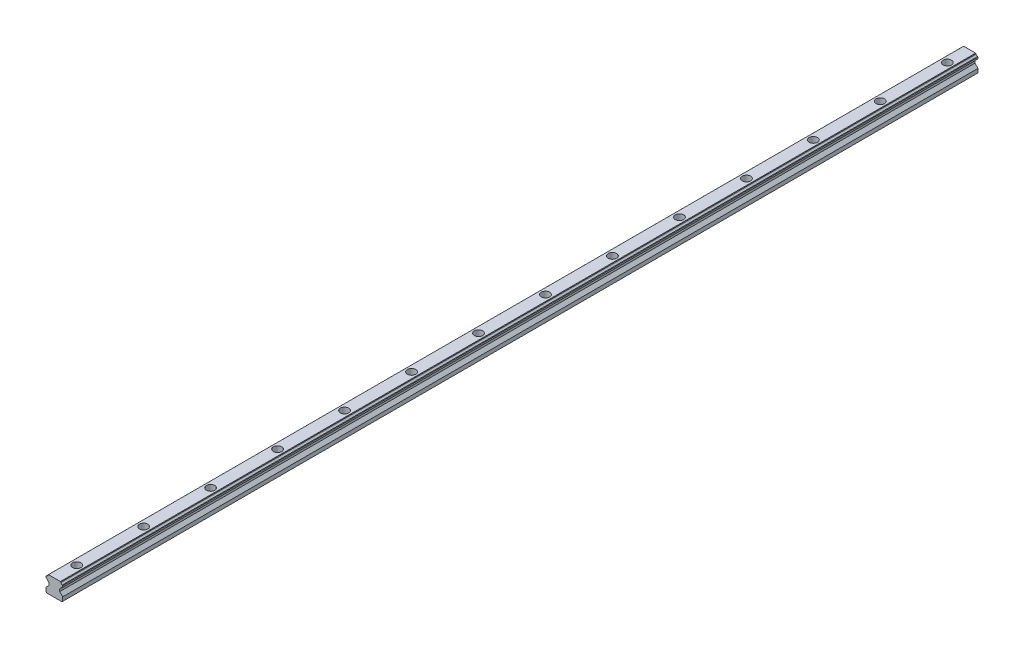
SolidWorks part; units mm, degrees
ref_plane "Front Plane" through (0, 0, 0) normal (0, 0, 1) x (1, 0, 0)
ref_plane "Top Plane" through (0, 0, 0) normal (0, 1, 0) x (1, 0, 0)
ref_plane "Right Plane" through (0, 0, 0) normal (1, 0, 0) x (0, 0, -1)
sketch "Sketch1" plane through (-20, 0, 0) normal (0, 0, 1) x (1, 0, 0)
  line L0 (12.5, 0.7) -> (13.2, 0)
  line L1 (13.2, 0) -> (26.8, 0)
  line L2 (27.5, 4.2) -> (27.5, 0.7)
  line L3 (24.8, 6.9) -> (27.5, 4.2)
  line L4 (24.8, 8.84) -> (24.8, 6.9)
  line L5 (25.7559, 9.7942) -> (24.8, 8.84)
  line L6 (27.5, 11.54) -> (27.0943, 11.1343)
  line L7 (27.5, 12.85) -> (27.5, 11.54)
  line L8 (27.0943, 13.2684) -> (27.5, 12.85)
  line L9 (25.35, 15) -> (25.7559, 14.5941)
  line L10 (27.5, 0.7) -> (26.8, 0)
  line L11 (25.35, 15) -> (14.65, 15)
  line L12 (14.65, 15) -> (14.2441, 14.5941)
  line L13 (12.9057, 13.2684) -> (12.5, 12.85)
  line L14 (12.5, 12.85) -> (12.5, 11.54)
  line L15 (12.5, 11.54) -> (12.9057, 11.1343)
  line L16 (14.2441, 9.7942) -> (15.2, 8.84)
  line L17 (15.2, 8.84) -> (15.2, 6.9)
  line L18 (15.2, 6.9) -> (12.5, 4.2)
  line L19 (12.5, 4.2) -> (12.5, 0.7)
  line L20 (20, 15) -> (20, 0) construction
  arc A0 (27.0943, 11.1343) -> (25.7559, 9.7942) centre (27.3023, 9.5882) ccw
  arc A1 (25.7559, 14.5941) -> (27.0943, 13.2684) centre (27.3003, 14.8148) ccw
  arc A2 (14.2441, 14.5941) -> (12.9057, 13.2684) centre (12.6997, 14.8148) cw
  arc A3 (12.9057, 11.1343) -> (14.2441, 9.7942) centre (12.6977, 9.5882) cw
  dimension "D14" = 1.56
  dimension "D1" = 15
  dimension "D2" = 0.7
  dimension "D3" = 0.7
  dimension "D4" = 4.2
  dimension "D5" = 6.9
  dimension "D6" = 8.84
  dimension "D7" = 4.8
  dimension "D8" = 5.7559
  dimension "D9" = 0.4059
  dimension "D10" = 0.4059
  dimension "D11" = 1.7316
  dimension "D12" = 2.15
  dimension "D13" = 3.46
  dimension "D15" = 7.0943
  dimension "D16" = 3.8657
  dimension "D17" = 5.2058
  dimension "D18" = 15
extrude "Extrude1" add sketch "Sketch1" against normal blind 820
sketch "Sketch2" plane through (0, 0, 0) normal (1, 0, 0) x (0, 0, -1)
  line L0 (20, 15) -> (23.75, 15)
  line L1 (23.75, 15) -> (23.75, 9.7)
  line L2 (23.75, 9.7) -> (22.25, 9.7)
  line L3 (22.25, 9.7) -> (22.25, 0)
  line L4 (22.25, 0) -> (20, 0)
  line L5 (20, 0) -> (20, 15) construction
  line L6 (20, 0) -> (20, 15) construction
  line L7 (20, 15) -> (20, 0)
  line L8 (820, 0) -> (0, 0) construction
  line L9 (820, 15) -> (0, 15) construction
  dimension "D1" = 5.3
  dimension "D2" = 7.5
  dimension "D3" = 4.5
  dimension "D4" = 20
revolve "Cut-Revolve1" cut sketch "Sketch2" angle 360 about L6 reverse direction yes
ref_axis "Axis1" through (0, 0, -168) along (0, 0, 1)
pattern_linear "LPattern1" count 14 spacing 60 along (0, 0, -1) of "Cut-Revolve1"
